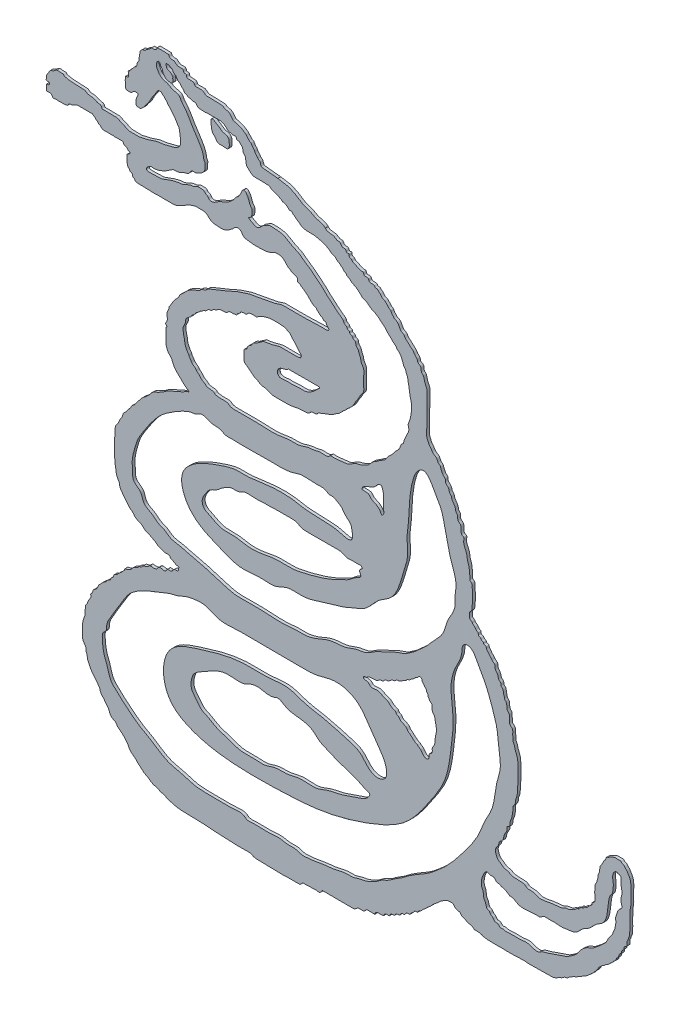
SolidWorks part; units mm, degrees
ref_plane "Front Plane" through (0, 0, 0) normal (0, 0, 1) x (1, 0, 0)
ref_plane "Top Plane" through (0, 0, 0) normal (0, 1, 0) x (1, 0, 0)
ref_plane "Right Plane" through (0, 0, 0) normal (1, 0, 0) x (0, 0, -1)
sketch "Sketch2" plane through (0, 0, 0) normal (0, 0, 1) x (1, 0, 0)
  line L0 (-17.7353, 62.4626) -> (-17.6834, 62.4327)
  arc A0 (-5.3453, 80.996) -> (-5.3626, 81.0286) centre (-5.3721, 81.0026) ccw
  spline S0 degree 3 number of poles 254 (-70.7479, 88.8825) -> (-17.7353, 62.4626)
  spline S1 degree 3 number of poles 909 (-17.6834, 62.4327) -> (-5.3453, 80.996)
  spline S2 degree 3 number of poles 170 (-21.9113, 87.7676) -> (-70.7479, 88.8825)
  spline S3 degree 3 number of poles 588 (-63.924, 102.1589) -> (-63.924, 102.1589)
  spline S4 degree 3 poles (-44.221, 94.2882) (-45.4116, 94.353) (-45.2516, 92.7115) (-45.1225, 91.4817) (-44.8417, 90.0857) (-43.7319, 89.332) (-43.2299, 87.9839) (-41.7677, 87.9079) (-40.6397, 88.0097) (-39.3603, 87.653) (-38.7939, 88.9636) (-38.942, 90.0423) (-38.9383, 91.17) (-39.8785, 91.9867) (-40.9697, 92.0508) (-41.9633, 92.6727) (-42.6749, 93.2743) (-43.6163, 93.7248) (-44.221, 94.2882) (-45.4116, 94.353) (-45.2516, 92.7115) knots -0.118877 -0.079113 -0.023135 0 0.073293 0.138607 0.209324 0.261424 0.329033 0.396722 0.447899 0.505187 0.559054 0.617022 0.671938 0.712291 0.784924 0.825496 0.881123 0.920887 0.976865 1 1.073293 1.138607 1.209324 only from (-44.9709, 94.273) to (-44.9709, 94.273)
  spline S5 degree 3 poles (14.3659, 13.0282) (13.0148, 12.954) (12.2866, 11.6004) (10.6422, 10.6743) (9.1177, 10.1404) (7.9608, 9.631) (7.1627, 8.4406) (8.6168, 8.3196) (9.8425, 8.4167) (10.7205, 6.8627) (12.1014, 6.6187) (13.1361, 5.7618) (13.8353, 5.1431) (14.3101, 3.7631) (15.3374, 5.0841) (14.7858, 6.3186) (14.9539, 7.9454) (14.9148, 9.3883) (14.9944, 10.7912) (14.7237, 11.8798) (14.3659, 13.0282) (13.0148, 12.954) (12.2866, 11.6004) knots -0.11095 -0.063569 -0.018382 0 0.077568 0.137052 0.218325 0.257205 0.297924 0.323187 0.389815 0.438109 0.50544 0.54238 0.588904 0.625333 0.658779 0.720108 0.777879 0.843534 0.88905 0.936431 0.981618 1 1.077568 1.137052 1.218325 only from (13.5986, 12.9563) to (13.5986, 12.9563)
  spline S6 degree 3 number of poles 122 (8.0191, -48.0387) -> (8.0191, -48.0387)
  spline S7 degree 3 number of poles 103 (51.2507, -85.3995) -> (51.2507, -85.3995)
  spline S8 degree 3 poles (-5.3626, 81.0286) (-5.3705, 81.0464) (-5.4397, 81.1764) (-6.2011, 81.7385) (-7.4735, 82.1171) (-9.1377, 82.5) (-10.2799, 83.3436) (-11.6262, 83.7456) (-12.8439, 84.1438) (-14.1421, 84.9191) (-15.2587, 85.7426) (-16.6112, 86.4229) (-17.9966, 87.076) (-18.9794, 87.3021) (-21.5141, 87.7044) (-21.9113, 87.7676) knots 0.924823 0.924823 0.924823 0.924823 0.92513 0.927093 0.936103 0.943205 0.949105 0.954472 0.961573 0.965891 0.974321 0.979642 0.986221 0.992639 1 1 1 1
  spline S9 degree 3 poles (6.019, -14.9228) (7.0303, -14.6847) (7.9805, -15.5619) (5.9472, -16.2737) (7.7866, -18.3363) (4.837, -19.3712) (3.2534, -21.0948) (0.0899, -22.5826) (-3.1819, -24.206) (-7.7293, -25.7872) (-12.0058, -26.8946) (-17.3291, -28.0544) (-22.5233, -27.3495) (-27.8207, -28.7411) (-32.3305, -28.9533) (-36.9415, -27.668) (-41.5612, -28.462) (-45.0838, -26.2203) (-47.7911, -25.2961) (-48.7059, -22.4765) (-47.301, -20.2518) (-45.705, -17.9977) (-43.4319, -17.4181) (-41.8811, -15.9146) (-40.1189, -14.7355) (-38.1242, -13.7002) (-35.7454, -14.211) (-33.5939, -12.5065) (-31.0235, -12.9703) (-28.7875, -12.9461) (-26.9642, -12.7726) (-25.0172, -12.8583) (-23.2477, -12.6896) (-21.286, -12.7203) (-19.4916, -12.7071) (-17.4416, -12.717) (-15.407, -12.687) (-13.8807, -13.8733) (-11.8365, -14.0611) (-9.8126, -13.9851) (-7.2129, -14.0096) (-4.6956, -13.9878) (-2.1168, -14.0362) (0.1456, -13.8843) (2.2062, -15.1944) (4.3419, -14.7069) (6.019, -14.9228) (7.0303, -14.6847) (7.9805, -15.5619) knots -0.040979 -0.018817 -0.005854 0 0.005914 0.016574 0.030272 0.047513 0.070847 0.092739 0.129596 0.160678 0.209162 0.237213 0.292416 0.333525 0.369496 0.400431 0.449469 0.474908 0.501238 0.513139 0.541481 0.559852 0.578927 0.595321 0.611559 0.630894 0.647625 0.666732 0.691825 0.707297 0.721539 0.736174 0.754592 0.764628 0.783863 0.79808 0.81489 0.831537 0.842537 0.863863 0.881007 0.905679 0.924914 0.94419 0.959021 0.981183 0.994146 1 1.005914 1.016574 1.030272 only from (7.0322, -14.8272) to (7.0322, -14.8272)
  spline S10 degree 3 poles (8.9678, -84.5113) (10.7827, -82.2553) (8.549, -81.7308) (6.7808, -80.6553) (3.4444, -79.2592) (-0.3729, -78.4034) (-4.0318, -76.4892) (-7.3783, -75.5104) (-9.8272, -72.6311) (-14.1769, -71.5313) (-18.5026, -71.5811) (-21.4964, -69.0307) (-24.0011, -70.2094) (-26.298, -69.9913) (-29.036, -69.3483) (-31.4439, -69.7498) (-33.8566, -71.3086) (-37.1494, -71.0944) (-41.0674, -70.7742) (-45.1325, -72.679) (-48.5445, -74.687) (-51.3971, -76.4311) (-52.2031, -79.0297) (-52.454, -81.6895) (-50.3563, -83.9792) (-48.8722, -86.3783) (-46.1226, -87.277) (-44.1801, -88.7604) (-41.2736, -89.8247) (-38.2271, -90.8088) (-34.5347, -92.0767) (-30.5119, -91.6529) (-26.4986, -92.3027) (-22.6149, -90.513) (-18.508, -91.0757) (-13.7897, -89.328) (-8.8781, -90.5995) (-4.4872, -88.3272) (-0.4987, -87.859) (3.2411, -86.4858) (6.5408, -85.3778) (8.9678, -84.5113) (10.7827, -82.2553) (8.549, -81.7308) knots -0.061997 -0.031698 -0.014921 0 0.00862 0.024465 0.048495 0.084562 0.109043 0.137664 0.157714 0.188013 0.229871 0.252424 0.258957 0.287228 0.300044 0.319844 0.337905 0.360461 0.388581 0.422321 0.453777 0.476713 0.490061 0.511412 0.530188 0.554586 0.570122 0.590663 0.607073 0.6365 0.660399 0.690149 0.722893 0.745694 0.779551 0.80927 0.851971 0.881722 0.912562 0.938003 0.968302 0.985079 1 1.00862 1.024465 1.048495 only from (10.1043, -82.306) to (10.1043, -82.306)
  spline S11 degree 3 poles (-8.2499, 31.9196) (-6.6328, 32.133) (-8.5184, 30.4989) (-9.5161, 29.5562) (-10.8492, 28.6351) (-12.6656, 27.9962) (-14.9295, 28.33) (-17.0324, 27.8671) (-19.2842, 28.2081) (-21.2541, 27.4464) (-22.1932, 28.8431) (-22.0649, 29.7564) (-21.5437, 30.6043) (-20.4964, 31.073) (-19.4804, 31.2148) (-18.6692, 31.5524) (-18.2139, 32.023) (-17.2281, 31.8742) (-15.9722, 31.9796) (-14.4871, 31.948) (-13.2311, 31.953) (-12.0111, 31.9528) (-10.611, 31.9468) (-9.2454, 31.97) (-8.2499, 31.9196) (-6.6328, 32.133) (-8.5184, 30.4989) knots -0.100058 -0.050973 -0.024543 0 0.059115 0.093215 0.149766 0.198422 0.26733 0.354358 0.390278 0.479089 0.503704 0.528319 0.55974 0.590559 0.629479 0.653545 0.670563 0.684722 0.739471 0.788556 0.819706 0.854632 0.899942 0.949027 0.975457 1 1.059115 1.093215 1.149766 only from (-7.3617, 31.9521) to (-7.3617, 31.9521)
  spline S12 degree 3 poles (-5.3969, 81.0909) (-5.3945, 81.0875) (-5.3894, 81.0793) (-5.381, 81.0651) knots 0.999946 0.999946 0.999946 0.999946 1 1 1 1
  spline S13 degree 3 number of poles 134 (28.8623, 24.7917) -> (28.8623, 24.7917)
  spline S14 degree 3 number of poles 122 (44.5069, -20.3141) -> (44.5069, -20.3141)
extrude "Boss-Extrude1" add sketch "Sketch2" along normal blind 1 contours S6 | S3 | S0 L0 S1 A0 S8 S2 | S4 | S11 | S5 | S13 | S9 | S14 | S10 | S7 region at (23.9316, -47.8751, 0)
